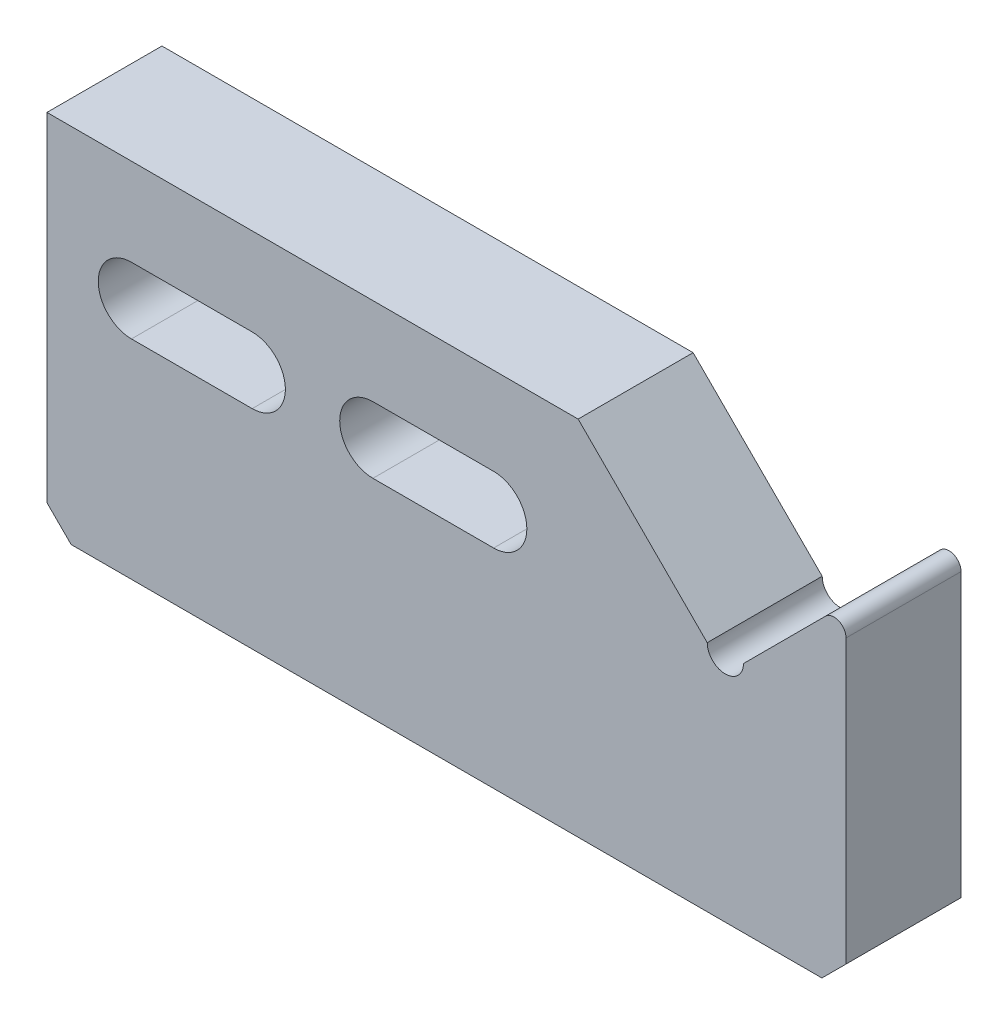
SolidWorks part; units mm, degrees
material "Plain Carbon Steel"
ref_plane "Front Plane" through (0, 0, 0) normal (0, 0, 1) x (1, 0, 0)
ref_plane "Top Plane" through (0, 0, 0) normal (0, 1, 0) x (1, 0, 0)
ref_plane "Right Plane" through (0, 0, 0) normal (1, 0, 0) x (0, 0, -1)
sketch "Sketch1" plane through (0, 0, 0) normal (0, 0, 1) x (1, 0, 0)
  line L0 (-10, 267.2189) -> (-18.5, 258.7189) construction
  line L1 (-10, 267.2189) -> (-10, 239.4113) construction
  line L2 (-10, 239.4113) -> (-76.1924, 239.4113) construction
  line L3 (-32.1924, 269.4113) -> (-21.5, 258.7189) construction
  line L4 (-76.1924, 269.4113) -> (-32.1924, 269.4113) construction
  line L5 (-76.1924, 239.4113) -> (-76.1924, 269.4113) construction
  line L6 (-59.1924, 262.1613) -> (-69.1924, 262.1613) construction
  line L7 (-39.1924, 262.1613) -> (-49.1924, 262.1613) construction
  line L8 (-55.3264, 249.4113) -> (-89.1924, 249.4113) construction
  line L9 (-10, 267.2189) -> (-18.5, 258.7189)
  line L10 (-10, 267.2189) -> (-10, 239.4113)
  line L11 (-10, 239.4113) -> (-76.1924, 239.4113)
  line L12 (-32.1924, 269.4113) -> (-21.5, 258.7189)
  line L13 (-76.1924, 269.4113) -> (-32.1924, 269.4113)
  line L14 (-76.1924, 239.4113) -> (-76.1924, 269.4113)
  line L15 (-59.1924, 262.1613) -> (-69.1924, 262.1613)
  line L16 (-39.1924, 262.1613) -> (-49.1924, 262.1613)
  line L17 (-55.3264, 249.4113) -> (-89.1924, 249.4113) construction
  line L18 (-56.1924, 250.9113) -> (-76.1924, 250.9113) construction
  line L19 (-56.1924, 250.9113) -> (-76.1924, 250.9113) construction
  line L20 (-39.1924, 256.6613) -> (-49.1924, 256.6613) construction
  line L21 (-59.1924, 256.6613) -> (-69.1924, 256.6613) construction
  line L22 (-39.1924, 256.6613) -> (-49.1924, 256.6613)
  line L23 (-59.1924, 256.6613) -> (-69.1924, 256.6613)
  arc A0 (-21.5, 258.7189) -> (-18.5, 258.7189) centre (-20, 258.7189) ccw construction
  arc A1 (-21.5, 258.7189) -> (-18.5, 258.7189) centre (-20, 258.7189) ccw
  arc A2 (-39.1924, 256.6613) -> (-39.1924, 262.1613) centre (-39.1924, 259.4113) ccw construction
  arc A3 (-49.1924, 262.1613) -> (-49.1924, 256.6613) centre (-49.1924, 259.4113) ccw construction
  arc A4 (-59.1924, 256.6613) -> (-59.1924, 262.1613) centre (-59.1924, 259.4113) ccw construction
  arc A5 (-69.1924, 262.1613) -> (-69.1924, 256.6613) centre (-69.1924, 259.4113) ccw construction
  arc A6 (-39.1924, 256.6613) -> (-39.1924, 262.1613) centre (-39.1924, 259.4113) ccw
  arc A7 (-49.1924, 262.1613) -> (-49.1924, 256.6613) centre (-49.1924, 259.4113) ccw
  arc A8 (-59.1924, 256.6613) -> (-59.1924, 262.1613) centre (-59.1924, 259.4113) ccw
  arc A9 (-69.1924, 262.1613) -> (-69.1924, 256.6613) centre (-69.1924, 259.4113) ccw
extrude "Boss-Extrude1" add sketch "Sketch1" along normal blind 6 and the other way blind 3.525
fillet "Fillet1" radius 1 1 edges at (-10, 267.2189, 1.2375)
chamfer "Chamfer1" distance 2 angle 45 2 edges at (-76.1924, 239.4113, 1.2375) (-10, 239.4113, 1.2375)
ref_plane "Plane1" through (0, 0, 1.2375) normal (0, 0, -1) x (-1, 0, 0)
sketch "Sketch3" plane through (0, 0, 1.2375) normal (0, 0, -1) x (-1, 0, 0)
  line L0 (76.1924, 250.9113) -> (56.1924, 250.9113)
  line L1 (56.1924, 250.9113) -> (55.3264, 249.4113)
  line L2 (55.3264, 249.4113) -> (76.1924, 249.4113)
  line L3 (76.1924, 249.4113) -> (76.1924, 250.9113)
  line L4 (76.1924, 249.4113) -> (89.1924, 249.4113) construction
revolve "Cut-Revolve1" cut sketch "Sketch3" angle 360 about L4
chamfer "Chamfer2" distance 0.5 angle 45 1 edges at (-76.1924, 249.4113, -0.2625)
